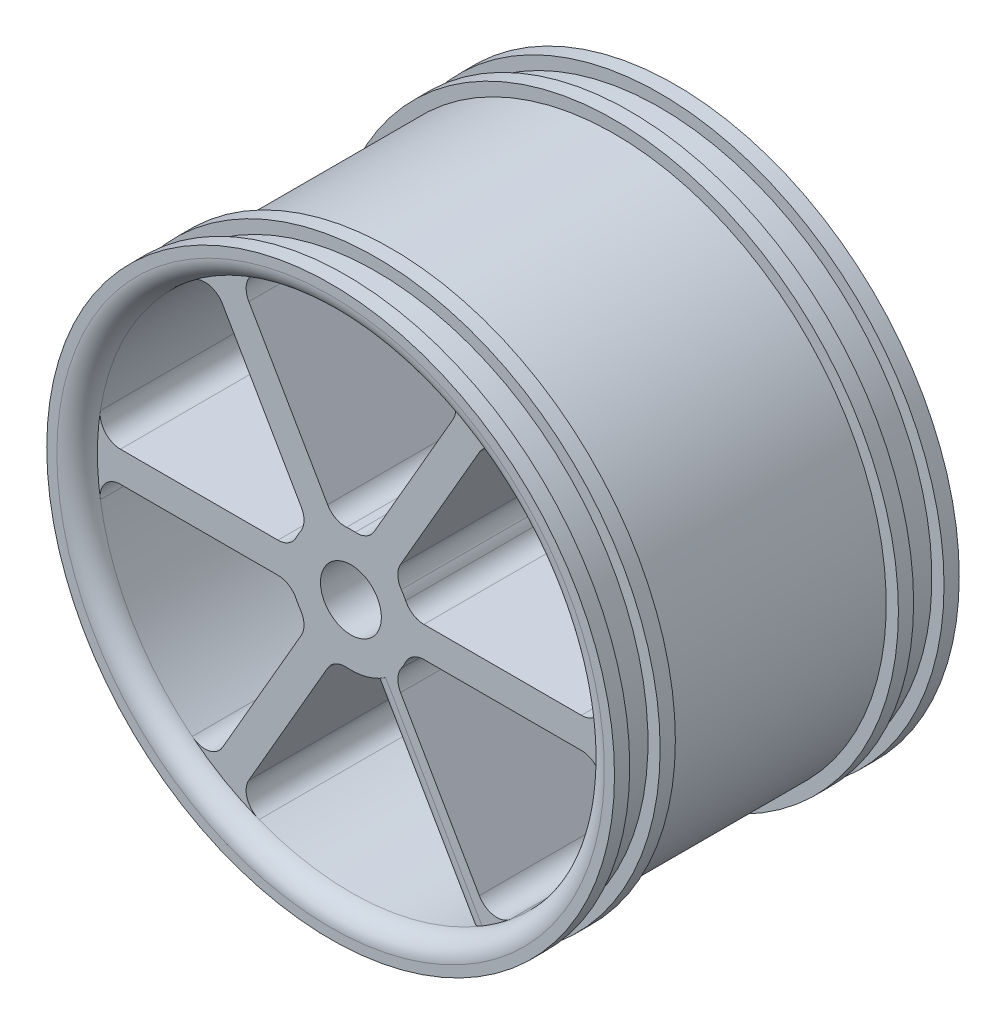
SolidWorks part; units mm, degrees
ref_plane "Front Plane" through (0, 0, 0) normal (0, 0, 1) x (1, 0, 0)
ref_plane "Top Plane" through (0, 0, 0) normal (0, 1, 0) x (1, 0, 0)
ref_plane "Right Plane" through (0, 0, 0) normal (1, 0, 0) x (0, 0, -1)
ref_plane "Plane1" through (0, 0, 0) normal (0, -1, 0) x (1, 0, 0)
sketch "Sketch1" plane through (0, 0, 0) normal (0, -1, 0) x (1, 0, 0)
  line L2 (25, 0) -> (28, 0)
  line L3 (28, 0) -> (28, 1.5)
  line L4 (28, 1.5) -> (26.8, 1.5)
  line L5 (26.8, 1.5) -> (26.8, 4.5)
  line L6 (26.8, 4.5) -> (28, 4.5)
  line L7 (28, 4.5) -> (28, 6)
  line L8 (28, 6) -> (26.8, 6)
  line L9 (26.8, 6) -> (26.8, 28)
  line L10 (26.8, 28) -> (28, 28)
  line L11 (28, 28) -> (28, 29.5)
  line L12 (28, 29.5) -> (26.8, 29.5)
  line L13 (26.8, 29.5) -> (26.8, 32.5)
  line L14 (26.8, 32.5) -> (28, 32.5)
  line L15 (28, 32.5) -> (28, 34)
  line L16 (0, 34) -> (0, 0) construction
  line L17 (25, 0) -> (25, 32)
  line L19 (0, 0) -> (25, 0) construction
  line L20 (27, 34) -> (28, 34)
  arc A0 (25, 32) -> (27, 34) centre (27, 32) cw
  dimension "D5" = 2
  dimension "D1" = 1.5
  dimension "D2" = 1.2
  dimension "D3" = 3
  dimension "D4" = 25
  dimension "D6" = 32
  dimension "D7" = 3
  dimension "D8" = 1.2
  dimension "D9" = 1.5
  dimension "D10" = 22
  dimension "D11" = 3
  dimension "D12" = 1.5
  dimension "D13" = 25
revolve "Revolve1" add sketch "Sketch1" angle 360 about L16
sketch "Sketch2" plane through (0, 0, 0) normal (0, 0, 1) x (1, 0, 0)
  line L0 (25, 0) -> (0, 0) construction
  line L1 (25, 1.5) -> (0, 1.5)
  line L2 (25, 1.5) -> (25, -1.5)
  line L3 (0, 1.5) -> (0, -1.5)
  line L4 (25, -1.5) -> (0, -1.5)
  line L5 (25, 1.5) -> (0, -1.5) construction
  line L6 (0, 1.5) -> (25, -1.5) construction
  circle A0 centre (0, 0) radius 25 construction
  circle A1 centre (0, 0) radius 25 construction
  point P3 (25, 0)
  point P6 (12.5, 0)
  dimension "D1" = 25
  dimension "D2" = 3
extrude "Boss-Extrude1" add sketch "Sketch2" along normal blind 32
pattern_circular "CirPattern1" count 6 over 360 about axis through (0, 0, 0) along (0, 0, 1) of "Boss-Extrude1"
sketch "Sketch5" plane through (0, 0, 0) normal (0, 0, 1) x (1, 0, 0)
  circle A0 centre (0, 0) radius 6
  dimension "D1" = 12
extrude "Boss-Extrude2" add sketch "Sketch5" along normal blind 32
sketch "Sketch6" plane through (0, 0, 0) normal (0, 0, 1) x (1, 0, 0)
  circle A0 centre (0, 0) radius 3
  dimension "D1" = 6
extrude "AxleHole" cut sketch "Sketch6" along normal through all
fillet "Fillet1" radius 2 22 edges at (-24.955, -1.5, 16) (-13.7765, -20.8616, 16) (-11.1784, -22.3616, 16) (13.7765, 20.8616, 16) (13.7765, -20.8616, 16) (5.8095, 1.5, 16) (4.2038, 4.2812, 16) (5.8095, -1.5, 16) (4.2038, -4.2812, 16) (1.6057, 5.7812, 16) (-1.6057, 5.7812, 16) (-4.2038, 4.2812, 16) (-5.8095, 1.5, 16) (-5.8095, -1.5, 16) (-4.2038, -4.2812, 16) (-1.6057, -5.7812, 16) (24.955, 1.5, 16) (24.955, -1.5, 16) (11.1784, 22.3616, 16) (-11.1784, 22.3616, 16) (-13.7765, 20.8616, 16) (-24.955, 1.5, 16)
